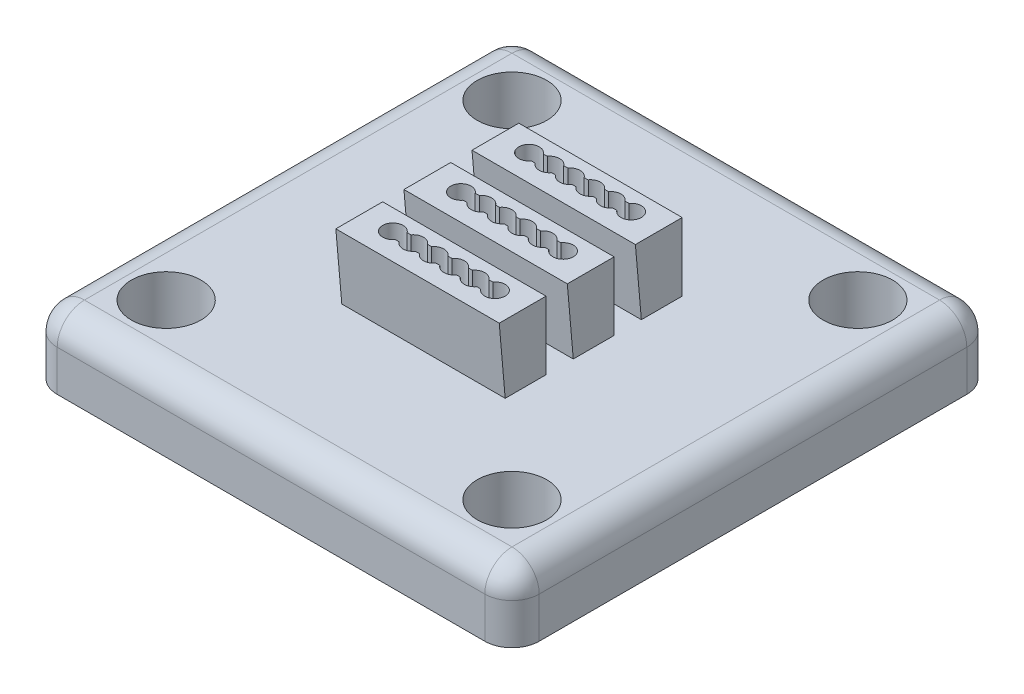
SolidWorks part; units mm, degrees
ref_plane "Front Plane" through (0, 0, 0) normal (0, 0, 1) x (1, 0, 0)
ref_plane "Top Plane" through (0, 0, 0) normal (0, 1, 0) x (1, 0, 0)
ref_plane "Right Plane" through (0, 0, 0) normal (1, 0, 0) x (0, 0, -1)
sketch "Sketch1" plane through (0, 0, 0) normal (0, 1, 0) x (1, 0, 0)
  line L4 (-2.7285, -3.0927) -> (-5.7285, -3.0927)
  line L5 (-5.7285, -3.0927) -> (-5.7285, -6.0927)
  line L6 (-17.4285, -12.2927) -> (-17.4285, 16.1073)
  line L7 (-15.4285, 18.1073) -> (15.9715, 18.1073)
  line L8 (3.2715, -6.0927) -> (6.2715, -6.0927)
  line L9 (17.9715, -12.2927) -> (17.9715, 16.1073)
  line L10 (17.9715, -12.2927) -> (17.9715, -15.2927)
  line L11 (15.9715, -17.2927) -> (-15.4285, -17.2927)
  line L12 (-17.4285, -15.2927) -> (-17.4285, -12.2927)
  line L13 (6.2715, -6.0927) -> (6.2715, -3.0927)
  line L14 (6.2715, -3.0927) -> (-2.7285, -3.0927)
  line L15 (-5.7285, -6.0927) -> (3.2715, -6.0927)
  line L16 (-2.7285, 1.9073) -> (-5.7285, 1.9073)
  line L17 (-5.7285, 1.9073) -> (-5.7285, -1.0927)
  line L18 (-5.7285, -1.0927) -> (6.2715, -1.0927)
  line L19 (6.2715, -1.0927) -> (6.2715, 1.9073)
  line L20 (6.2715, 1.9073) -> (-2.7285, 1.9073)
  line L21 (-5.7285, 3.9073) -> (-5.7285, 6.9073)
  line L22 (-5.7285, 6.9073) -> (6.2715, 6.9073)
  line L23 (6.2715, 6.9073) -> (6.2715, 3.9073)
  line L24 (6.2715, 3.9073) -> (-5.7285, 3.9073)
  circle A0 centre (-12.4285, -12.2927) radius 2.5527
  circle A1 centre (12.9715, -12.2927) radius 2.5527
  circle A2 centre (12.9715, 13.1073) radius 2.5527
  circle A3 centre (-12.4285, 13.1073) radius 2.5527
  arc A4 (-15.4285, -17.2927) -> (-17.4285, -15.2927) centre (-15.4285, -15.2927) cw
  arc A5 (17.9715, -15.2927) -> (15.9715, -17.2927) centre (15.9715, -15.2927) cw
  arc A6 (17.9715, 16.1073) -> (15.9715, 18.1073) centre (15.9715, 16.1073) ccw
  arc A7 (-17.4285, 16.1073) -> (-15.4285, 18.1073) centre (-15.4285, 16.1073) cw
  arc A14 (0.4215, 4.9573) -> (1.6215, 4.9573) centre (1.0215, 5.4073) ccw
  arc A15 (-1.0785, 4.9573) -> (0.1215, 4.9573) centre (-0.4785, 5.4073) ccw
  arc A16 (-2.5785, 4.9573) -> (-1.3785, 4.9573) centre (-1.9785, 5.4073) ccw
  arc A17 (1.9215, 4.9573) -> (3.1215, 4.9573) centre (2.5215, 5.4073) ccw
  arc A18 (3.4215, 4.9573) -> (3.4215, 5.8573) centre (4.0215, 5.4073) ccw
  arc A19 (-2.8785, 5.8573) -> (-2.8785, 4.9573) centre (-3.4785, 5.4073) ccw
  arc A20 (-2.8785, 5.8573) -> (-2.5785, 5.8573) centre (-2.7285, 6.9073) ccw
  arc A21 (-1.3785, 5.8573) -> (-1.0785, 5.8573) centre (-1.2285, 6.9073) ccw
  arc A22 (0.4215, 5.8573) -> (0.1215, 5.8573) centre (0.2715, 6.9073) cw
  arc A23 (1.9215, 5.8573) -> (1.6215, 5.8573) centre (1.7715, 6.9073) cw
  arc A24 (3.1215, 5.8573) -> (3.4215, 5.8573) centre (3.2715, 6.9073) ccw
  arc A25 (3.4215, 4.9573) -> (3.1215, 4.9573) centre (3.2715, 3.9073) ccw
  arc A26 (1.9215, 4.9573) -> (1.6215, 4.9573) centre (1.7715, 3.9073) ccw
  arc A27 (0.4215, 4.9573) -> (0.1215, 4.9573) centre (0.2715, 3.9073) ccw
  arc A28 (-1.0785, 4.9573) -> (-1.3785, 4.9573) centre (-1.2285, 3.9073) ccw
  arc A29 (-2.5785, 4.9573) -> (-2.8785, 4.9573) centre (-2.7285, 3.9073) ccw
  arc A30 (-1.3785, 5.8573) -> (-2.5785, 5.8573) centre (-1.9785, 5.4073) ccw
  arc A31 (0.1215, 5.8573) -> (-1.0785, 5.8573) centre (-0.4785, 5.4073) ccw
  arc A32 (1.6215, 5.8573) -> (0.4215, 5.8573) centre (1.0215, 5.4073) ccw
  arc A33 (3.1215, 5.8573) -> (1.9215, 5.8573) centre (2.5215, 5.4073) ccw
  arc A34 (3.1215, -0.0427) -> (1.9215, -0.0427) centre (2.5215, 0.4073) cw
  arc A35 (1.6215, -0.0427) -> (0.4215, -0.0427) centre (1.0215, 0.4073) cw
  arc A36 (0.1215, -0.0427) -> (-1.0785, -0.0427) centre (-0.4785, 0.4073) cw
  arc A37 (-1.3785, -0.0427) -> (-2.5785, -0.0427) centre (-1.9785, 0.4073) cw
  arc A38 (-2.5785, 0.8573) -> (-2.8785, 0.8573) centre (-2.7285, 1.9073) cw
  arc A39 (-1.0785, 0.8573) -> (-1.3785, 0.8573) centre (-1.2285, 1.9073) cw
  arc A40 (0.4215, 0.8573) -> (0.1215, 0.8573) centre (0.2715, 1.9073) cw
  arc A41 (1.9215, 0.8573) -> (1.6215, 0.8573) centre (1.7715, 1.9073) cw
  arc A42 (3.4215, 0.8573) -> (3.1215, 0.8573) centre (3.2715, 1.9073) cw
  arc A43 (3.1215, -0.0427) -> (3.4215, -0.0427) centre (3.2715, -1.0927) cw
  arc A44 (1.9215, -0.0427) -> (1.6215, -0.0427) centre (1.7715, -1.0927) ccw
  arc A45 (0.4215, -0.0427) -> (0.1215, -0.0427) centre (0.2715, -1.0927) ccw
  arc A46 (-1.3785, -0.0427) -> (-1.0785, -0.0427) centre (-1.2285, -1.0927) cw
  arc A47 (-2.8785, -0.0427) -> (-2.5785, -0.0427) centre (-2.7285, -1.0927) cw
  arc A48 (-2.8785, -0.0427) -> (-2.8785, 0.8573) centre (-3.4785, 0.4073) cw
  arc A49 (3.4215, 0.8573) -> (3.4215, -0.0427) centre (4.0215, 0.4073) cw
  arc A50 (1.9215, 0.8573) -> (3.1215, 0.8573) centre (2.5215, 0.4073) cw
  arc A51 (-2.5785, 0.8573) -> (-1.3785, 0.8573) centre (-1.9785, 0.4073) cw
  arc A52 (-1.0785, 0.8573) -> (0.1215, 0.8573) centre (-0.4785, 0.4073) cw
  arc A53 (0.4215, 0.8573) -> (1.6215, 0.8573) centre (1.0215, 0.4073) cw
  arc A54 (3.1215, -5.0427) -> (1.9215, -5.0427) centre (2.5215, -4.5927) cw
  arc A55 (1.6215, -5.0427) -> (0.4215, -5.0427) centre (1.0215, -4.5927) cw
  arc A56 (0.1215, -5.0427) -> (-1.0785, -5.0427) centre (-0.4785, -4.5927) cw
  arc A57 (-1.3785, -5.0427) -> (-2.5785, -5.0427) centre (-1.9785, -4.5927) cw
  arc A58 (-2.5785, -4.1427) -> (-2.8785, -4.1427) centre (-2.7285, -3.0927) cw
  arc A59 (-1.0785, -4.1427) -> (-1.3785, -4.1427) centre (-1.2285, -3.0927) cw
  arc A60 (0.4215, -4.1427) -> (0.1215, -4.1427) centre (0.2715, -3.0927) cw
  arc A61 (1.9215, -4.1427) -> (1.6215, -4.1427) centre (1.7715, -3.0927) cw
  arc A62 (3.4215, -4.1427) -> (3.1215, -4.1427) centre (3.2715, -3.0927) cw
  arc A63 (3.1215, -5.0427) -> (3.4215, -5.0427) centre (3.2715, -6.0927) cw
  arc A64 (1.9215, -5.0427) -> (1.6215, -5.0427) centre (1.7715, -6.0927) ccw
  arc A65 (0.4215, -5.0427) -> (0.1215, -5.0427) centre (0.2715, -6.0927) ccw
  arc A66 (-1.3785, -5.0427) -> (-1.0785, -5.0427) centre (-1.2285, -6.0927) cw
  arc A67 (-2.8785, -5.0427) -> (-2.5785, -5.0427) centre (-2.7285, -6.0927) cw
  arc A68 (-2.8785, -5.0427) -> (-2.8785, -4.1427) centre (-3.4785, -4.5927) cw
  arc A69 (3.4215, -4.1427) -> (3.4215, -5.0427) centre (4.0215, -4.5927) cw
  arc A70 (1.9215, -4.1427) -> (3.1215, -4.1427) centre (2.5215, -4.5927) cw
  arc A71 (-2.5785, -4.1427) -> (-1.3785, -4.1427) centre (-1.9785, -4.5927) cw
  arc A72 (-1.0785, -4.1427) -> (0.1215, -4.1427) centre (-0.4785, -4.5927) cw
  arc A73 (0.4215, -4.1427) -> (1.6215, -4.1427) centre (1.0215, -4.5927) cw
  point P22 (0, 0)
  point P23 (0, 0)
  point P37 (0.2715, 0.4073)
  point P42 (0.2715, 5.4073)
  point P46 (0.2715, -4.5927)
  point P49 (0.2715, 0.4073)
  dimension "D1" = 2
extrude "Boss-Extrude1" add sketch "Sketch1" along normal blind 5 contours A7 L6 L12 A4 L11 A5 L10 L9 A6 L7 A3 A2 A1 A0 L20 L19 L18 L17 L16 L15 L5 L4 L14 L13 L8 L23 L24 L21 L22 | L24 L23 L22 L21 A33 A24 A18 A25 A17 A26 A14 A27 A15 A28 A16 A29 A19 A20 A30 A21 A31 A22 A32 A23 | L19 L20 L16 L17 L18 A40 A53 A41 A50 A42 A49 A43 A34 A44 A35 A45 A36 A46 A37 A47 A48 A38 A51 A39 A52 | L5 L15 L8 L13 L14 L4 A60 A73 A61 A70 A62 A69 A63 A54 A64 A55 A65 A56 A66 A57 A67 A68 A58 A71 A59 A72 | A24 A33 A23 A32 A22 A31 A21 A30 A20 A19 A29 A16 A28 A15 A27 A14 A26 A17 A25 A18 | A53 A40 A52 A39 A51 A38 A48 A47 A37 A46 A36 A45 A35 A44 A34 A43 A49 A42 A50 A41 | A73 A60 A72 A59 A71 A58 A68 A67 A57 A66 A56 A65 A55 A64 A54 A63 A69 A62 A70 A61 region at (1.7715, 0, 3.2164) region at (-16.9279, 0, -1.9073) region at (1.7715, 0, -1.7836) region at (-5.6048, 0, -5.4073) region at (0.2715, 0, -5.4073) region at (0.2715, 0, -0.4073) region at (0.2715, 0, 4.5927)
extrude "Boss-Extrude2" add sketch "Sketch1<3>" along normal blind 10 contours L19 L20 L16 L17 L18 A40 A53 A41 A50 A42 A49 A43 A34 A44 A35 A45 A36 A46 A37 A47 A48 A38 A51 A39 A52 | L24 L23 L22 L21 A33 A24 A18 A25 A17 A26 A14 A27 A15 A28 A16 A29 A19 A20 A30 A21 A31 A22 A32 A23 | L5 L15 L8 L13 L14 L4 A60 A73 A61 A70 A62 A69 A63 A54 A64 A55 A65 A56 A66 A57 A67 A68 A58 A71 A59 A72 region at (1.7715, 0, 3.2164) region at (1.7715, 0, -1.7836) region at (-5.6048, 0, -5.4073)
sketch "Sketch1<3>" plane through (0, 0, 0) normal (0, 1, 0) x (1, 0, 0) same geometry as "Sketch1"
draft "Draft1" type of draft neutral plane draft angle 5 faces to draft 1 face at (0.2715, 7.5, 6.0927) neutral plane through (0, 5, 0) neutral plane normal (0, 1, 0) reverse direction yes parameters "D1"=5
draft "Draft2" type of draft neutral plane draft angle 5 faces to draft 1 face at (0.2715, 7.5, 1.0927) neutral plane through (0, 5, 0) neutral plane normal (0, 1, 0) reverse direction yes parameters "D1"=5
draft "Draft3" type of draft neutral plane draft angle 5 faces to draft 1 face at (0.2715, 7.5, -3.9073) neutral plane through (0, 5, 0) neutral plane normal (0, 1, 0) reverse direction yes parameters "D1"=5
fillet "Fillet1" radius 2 8 edges at (17.3857, 5, 16.7069) (17.9715, 5, -0.4073) (17.3857, 5, -17.5215) (0.2715, 5, -18.1073) (-16.8427, 5, -17.5215) (-17.4285, 5, -0.4073) (-16.8427, 5, 16.7069) (0.2715, 5, 17.2927)
